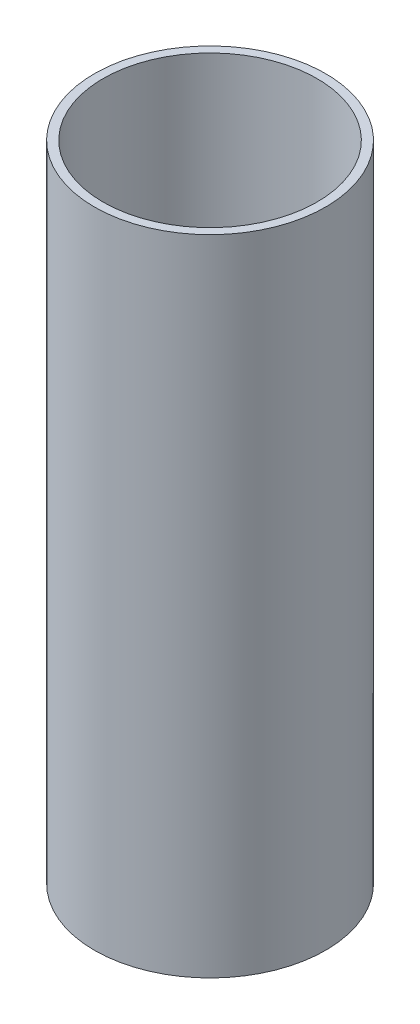
SolidWorks part; units mm, degrees
ref_plane "Front Plane" through (0, 0, 0) normal (0, 0, 1) x (1, 0, 0)
ref_plane "Top Plane" through (0, 0, 0) normal (0, 1, 0) x (1, 0, 0)
ref_plane "Right Plane" through (0, 0, 0) normal (1, 0, 0) x (0, 0, -1)
sketch "Sketch1" plane through (0, 0, 0) normal (0, 1, 0) x (1, 0, 0)
  circle A0 centre (0, 0) radius 37.4
  circle A1 centre (0, 0) radius 40.4
  dimension "D1" = 74.8
  dimension "D2" = 3
extrude "Boss-Extrude1" add sketch "Sketch1" along normal blind 225
